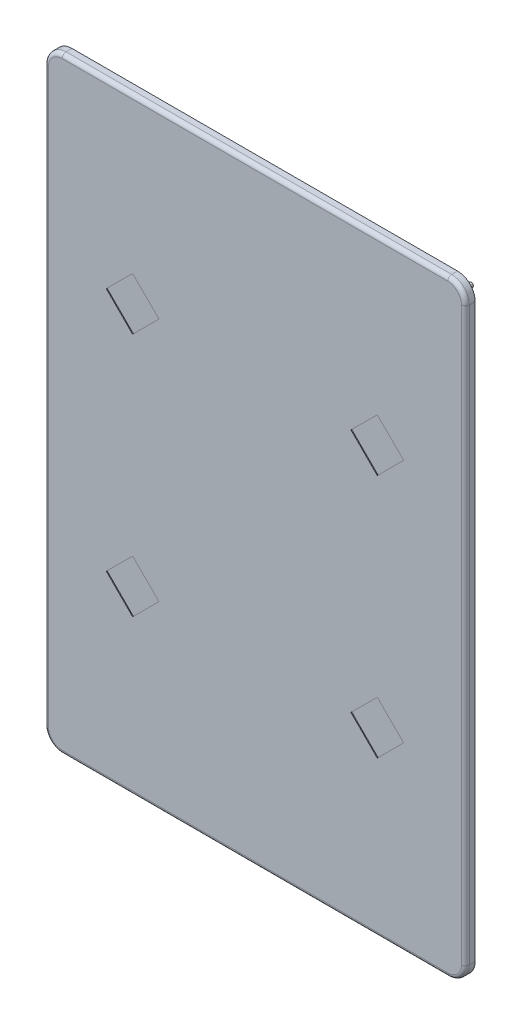
SolidWorks part; units mm, degrees
ref_plane "Front Plane" through (0, 0, 0) normal (0, 0, 1) x (1, 0, 0)
ref_plane "Top Plane" through (0, 0, 0) normal (0, 1, 0) x (1, 0, 0)
ref_plane "Right Plane" through (0, 0, 0) normal (1, 0, 0) x (0, 0, -1)
sketch "Sketch1" plane through (0, 0, 0) normal (0, 0, 1) x (1, 0, 0)
  line L1 (0, 0) -> (273.05, 0)
  line L2 (0, 0) -> (0, 393.7)
  line L3 (0, 393.7) -> (273.05, 393.7)
  line L4 (273.05, 0) -> (273.05, 393.7)
  dimension "D1" = 393.7
  dimension "D2" = 273.05
extrude "Boss-Extrude1" add sketch "Sketch1" along normal blind 6.35
fillet "Fillet2" radius 11.43 4 edges at (0, 0, 3.175) (273.05, 0, 3.175) (0, 393.7, 3.175) (273.05, 393.7, 3.175)
fillet "Fillet1" radius 2.54 8 edges at (136.525, 393.7, 6.35) (273.05, 196.85, 6.35) (136.525, 0, 6.35) (0, 196.85, 6.35) (3.3478, 390.3522, 6.35) (269.7022, 390.3522, 6.35) (269.7022, 3.3478, 6.35) (3.3478, 3.3478, 6.35)
sketch "Sketch2" plane through (0, 0, 0) normal (0, 0, -1) x (-1, 0, 0)
  line L0 (-265.811, 385.826) -> (-7.239, 385.826) construction
  line L1 (-7.239, 385.826) -> (-7.239, 7.874) construction
  line L2 (-7.239, 7.874) -> (-265.811, 7.874) construction
  line L3 (-265.811, 7.874) -> (-265.811, 385.826) construction
  line L4 (-136.525, 393.7) -> (-136.525, 385.826) construction
  line L5 (-261.62, 393.7) -> (-11.43, 393.7) construction
  line L6 (-273.05, 196.85) -> (-265.811, 196.85) construction
  line L7 (-273.05, 11.43) -> (-273.05, 382.27) construction
  circle A0 centre (-265.811, 385.826) radius 1.397
  circle A1 centre (-136.525, 385.826) radius 1.397
  circle A2 centre (-7.239, 385.826) radius 1.397
  circle A3 centre (-136.525, 196.85) radius 1.397 [skipped]
  circle A5 centre (-136.525, 7.874) radius 1.397
  circle A6 centre (-7.239, 7.874) radius 1.397
  circle A8 centre (-265.811, 7.874) radius 1.397
  circle A9 centre (-265.811, 196.85) radius 1.397 [skipped]
  circle A10 centre (-7.239, 196.85) radius 1.397 [skipped]
  dimension "D1" = 2.794
  dimension "D2" = 3
  dimension "D3" = 3
extrude "Boss-Extrude2" add sketch "Sketch2" along normal blind 4.699
ref_plane "Plane1" through (0, 9.779, 0) normal (0, -1, 0) x (-1, 0, 0)
sketch "Sketch3" plane through (0, 9.779, 0) normal (0, -1, 0) x (-1, 0, 0)
  line L0 (-240.03, 0) -> (-240.03, 0.254)
  line L1 (-11.43, 0) -> (-261.62, 0) construction
  line L2 (-240.03, 0.254) -> (-233.7435, 0.254)
  line L3 (-221.869, 0.254) -> (-221.869, 0)
  line L4 (-221.869, 0) -> (-240.03, 0)
  line L5 (-273.05, -3.81) -> (-273.05, 0) construction
  line L6 (-230.9495, 0.254) -> (-230.9495, 1.27) construction
  line L7 (-232.9815, 1.27) -> (-232.9815, 1.016)
  line L8 (-228.9175, 1.27) -> (-228.9175, 1.016)
  line L9 (-228.1555, 0.254) -> (-221.869, 0.254)
  arc A0 (-228.1555, 0.254) -> (-228.9175, 1.016) centre (-228.1555, 1.016) cw
  arc A1 (-228.9175, 1.27) -> (-232.9815, 1.27) centre (-230.9495, 1.27) ccw
  arc A2 (-233.7435, 0.254) -> (-232.9815, 1.016) centre (-233.7435, 1.016) ccw
  point P16 (-228.9175, 0.254)
  dimension "D4" = 0.762
  dimension "D1" = 18.161
  dimension "D2" = 33.02
  dimension "D3" = 0.254
  dimension "D5" = 1.27
extrude "Boss-Extrude3" add sketch "Sketch3" against normal blind 6.35
sketch "Sketch4" plane through (0, 0, 6.35) normal (0, 0, 1) x (1, 0, 0)
  line L0 (198.7917, 276.225) -> (215.9, 293.2416)
  line L1 (40.0417, 276.225) -> (57.15, 293.2416)
  line L2 (40.0417, 276.225) -> (57.15, 259.1167)
  line L3 (57.15, 259.1167) -> (74.2583, 276.225)
  line L4 (57.15, 293.2416) -> (74.2583, 276.225)
  line L5 (198.7917, 276.225) -> (215.9, 259.1167)
  line L6 (215.9, 259.1167) -> (233.0083, 276.225)
  line L7 (215.9, 293.2416) -> (233.0083, 276.225)
  line L8 (198.7917, 117.475) -> (215.9, 134.4916)
  line L9 (198.7917, 117.475) -> (215.9, 100.3667)
  line L10 (215.9, 100.3667) -> (233.0083, 117.475)
  line L11 (215.9, 134.4916) -> (233.0083, 117.475)
  line L12 (40.0417, 117.475) -> (57.15, 134.4916)
  line L13 (40.0417, 117.475) -> (57.15, 100.3667)
  line L14 (57.15, 100.3667) -> (74.2583, 117.475)
  line L15 (57.15, 134.4916) -> (74.2583, 117.475)
  line L16 (74.2583, 276.225) -> (198.7917, 276.225) construction
  line L17 (198.7917, 276.225) -> (198.7917, 117.475) construction
  line L18 (74.2583, 117.475) -> (198.7917, 117.475) construction
  line L19 (74.2583, 117.475) -> (74.2583, 276.225) construction
  line L20 (136.525, 391.16) -> (136.525, 276.225) construction
  line L21 (261.62, 391.16) -> (11.43, 391.16) construction
  line L22 (2.54, 196.85) -> (74.2583, 196.85) construction
  line L23 (2.54, 382.27) -> (2.54, 11.43) construction
  dimension "D1" = 24.13
  dimension "D2" = 24.13
  dimension "D3" = 2
  dimension "D4" = 2
extrude "Cut-Extrude1" cut sketch "Sketch4" against normal blind 0.508
